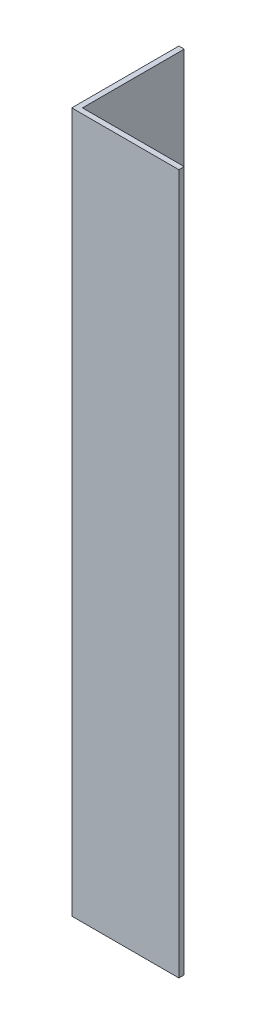
SolidWorks part; units mm, degrees
material "1060 Сплав"
ref_plane "Спереди" through (0, 0, 0) normal (0, 0, 1) x (1, 0, 0)
ref_plane "Сверху" through (0, 0, 0) normal (0, 1, 0) x (1, 0, 0)
ref_plane "Справа" through (0, 0, 0) normal (1, 0, 0) x (0, 0, -1)
sketch "Эскиз1" plane through (0, 0, 0) normal (0, 1, 0) x (1, 0, 0)
  line L0 (0, 0) -> (0, 15)
  line L1 (0, 15) -> (0.75, 15)
  line L2 (0.75, 15) -> (0.75, 0.75)
  line L3 (0.75, 0.75) -> (15, 0.75)
  line L4 (15, 0.75) -> (15, 0)
  line L5 (15, 0) -> (0, 0)
  dimension "D1" = 0.75
  dimension "D2" = 15
extrude "Бобышка-Вытянуть1" add sketch "Эскиз1" along normal blind 98
sketch "Эскиз2" plane through (0, 0, 0) normal (-1, 0, 0) x (0, 0, 1)
  line L0 (-7.5, 98) -> (-7.5, 0) construction
  line L1 (-15, 98) -> (0, 98) construction
  line L2 (-15, 0) -> (0, 0) construction
